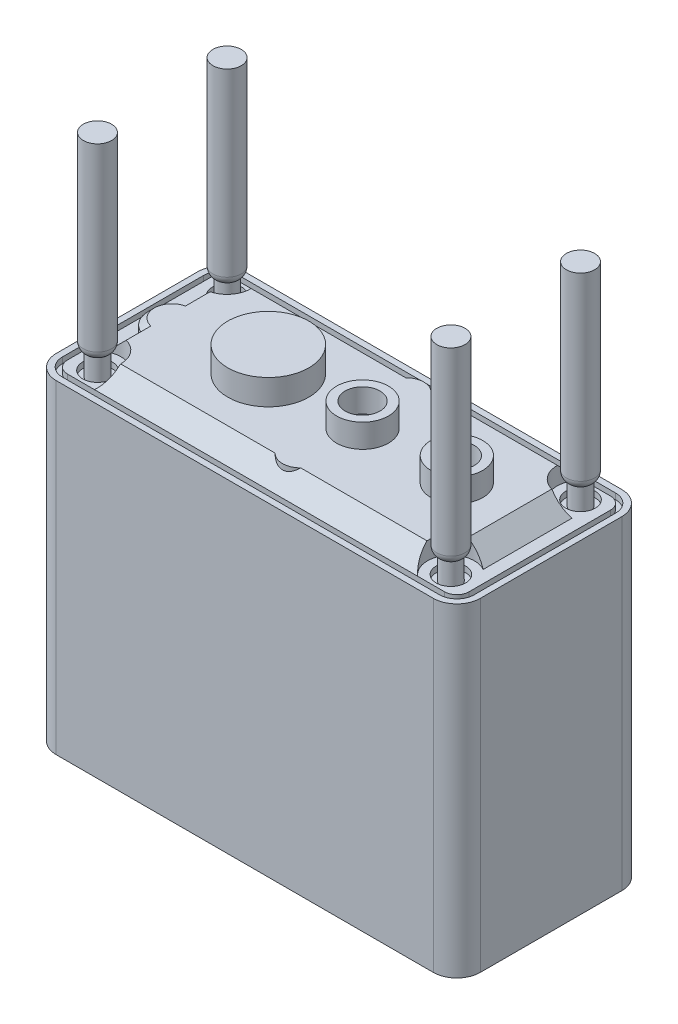
SolidWorks part; units mm, degrees
ref_plane "Front Plane" through (0, 0, 0) normal (0, 0, 1) x (1, 0, 0)
ref_plane "Top Plane" through (0, 0, 0) normal (0, 1, 0) x (1, 0, 0)
ref_plane "Right Plane" through (0, 0, 0) normal (1, 0, 0) x (0, 0, -1)
sketch "Sketch1" plane through (0, 0, 0) normal (0, 1, 0) x (1, 0, 0)
  line L1 (-28.575, 12.7) -> (28.575, 12.7)
  line L2 (-28.575, 12.7) -> (-28.575, -12.7)
  line L3 (-28.575, -12.7) -> (28.575, -12.7)
  line L4 (28.575, 12.7) -> (28.575, -12.7)
  line L5 (-28.575, 12.7) -> (28.575, -12.7) construction
  line L6 (-28.575, -12.7) -> (28.575, 12.7) construction
  point P0 (0, 0)
  dimension "D1" = 57.15
  dimension "D2" = 25.4
extrude "Boss-Extrude1" add sketch "Sketch1" along normal blind 43.6562
fillet "Fillet1" radius 3.175 4 edges at (-28.575, 21.8281, -12.7) (-28.575, 21.8281, 12.7) (28.575, 21.8281, -12.7) (28.575, 21.8281, 12.7)
sketch "Sketch2" plane through (0, 43.6562, 0) normal (0, 1, 0) x (1, 0, 0)
  line L8 (25.4, 11.8745) -> (-25.4, 11.8745)
  line L9 (-27.7495, 9.525) -> (-27.7495, -9.525)
  line L10 (-25.4, -11.8745) -> (25.4, -11.8745)
  line L11 (27.7495, -9.525) -> (27.7495, 9.525)
  line L12 (25.4, 11.8745) -> (-25.4, 11.8745)
  line L13 (-27.7495, 9.525) -> (-27.7495, -9.525)
  line L14 (-25.4, -11.8745) -> (25.4, -11.8745)
  line L15 (27.7495, -9.525) -> (27.7495, 9.525)
  line L20 (25.4, 11.176) -> (-25.4, 11.176)
  line L21 (-27.051, 9.525) -> (-27.051, -9.525)
  line L22 (-25.4, -11.176) -> (25.4, -11.176)
  line L23 (27.051, -9.525) -> (27.051, 9.525)
  line L24 (25.4, 11.176) -> (-25.4, 11.176)
  line L25 (-27.051, 9.525) -> (-27.051, -9.525)
  line L26 (-25.4, -11.176) -> (25.4, -11.176)
  line L27 (27.051, -9.525) -> (27.051, 9.525)
  arc A8 (-25.4, 11.8745) -> (-27.7495, 9.525) centre (-25.4, 9.525) ccw
  arc A9 (-27.7495, -9.525) -> (-25.4, -11.8745) centre (-25.4, -9.525) ccw
  arc A10 (25.4, -11.8745) -> (27.7495, -9.525) centre (25.4, -9.525) ccw
  arc A11 (27.7495, 9.525) -> (25.4, 11.8745) centre (25.4, 9.525) ccw
  arc A12 (-25.4, 11.8745) -> (-27.7495, 9.525) centre (-25.4, 9.525) ccw
  arc A13 (-27.7495, -9.525) -> (-25.4, -11.8745) centre (-25.4, -9.525) ccw
  arc A14 (25.4, -11.8745) -> (27.7495, -9.525) centre (25.4, -9.525) ccw
  arc A15 (27.7495, 9.525) -> (25.4, 11.8745) centre (25.4, 9.525) ccw
  arc A20 (-25.4, 11.176) -> (-27.051, 9.525) centre (-25.4, 9.525) ccw
  arc A21 (-27.051, -9.525) -> (-25.4, -11.176) centre (-25.4, -9.525) ccw
  arc A22 (25.4, -11.176) -> (27.051, -9.525) centre (25.4, -9.525) ccw
  arc A23 (27.051, 9.525) -> (25.4, 11.176) centre (25.4, 9.525) ccw
  arc A24 (-25.4, 11.176) -> (-27.051, 9.525) centre (-25.4, 9.525) ccw
  arc A25 (-27.051, -9.525) -> (-25.4, -11.176) centre (-25.4, -9.525) ccw
  arc A26 (25.4, -11.176) -> (27.051, -9.525) centre (25.4, -9.525) ccw
  arc A27 (27.051, 9.525) -> (25.4, 11.176) centre (25.4, 9.525) ccw
  dimension "D1" = 0.8255
  dimension "D2" = 1.524
extrude "Cut-Extrude1" cut sketch "Sketch2" against normal blind 0.7937
sketch "Sketch3" plane through (0, 43.6562, 0) normal (0, 1, 0) x (1, 0, 0)
  line L1 (23.8125, -8.7312) -> (-23.8125, -8.7313) construction
  line L2 (23.8125, -8.7312) -> (23.8125, 8.7313) construction
  line L3 (23.8125, 8.7313) -> (-23.8125, 8.7312) construction
  line L4 (-23.8125, -8.7313) -> (-23.8125, 8.7312) construction
  line L5 (23.8125, -8.7312) -> (-23.8125, 8.7312) construction
  line L6 (23.8125, 8.7313) -> (-23.8125, -8.7313) construction
  circle A0 centre (-23.8125, 8.7312) radius 1.9844
  circle A1 centre (-23.8125, -8.7313) radius 1.9844
  circle A2 centre (23.8125, -8.7312) radius 1.9844
  circle A3 centre (23.8125, 8.7313) radius 1.9844
  point P0 (0, 0)
  dimension "D1" = 3.9688
  dimension "D2" = 47.625
  dimension "D3" = 17.4625
extrude "Cut-Extrude2" cut sketch "Sketch3" against normal up to surface (0.7937 mm away) up to face at (0, 42.8625, 0)
sketch "Sketch4" plane through (0, 43.6562, 0) normal (0, 1, 0) x (1, 0, 0)
  line L1 (21.7867, -11.176) -> (-21.7867, -11.176)
  line L2 (25.4, -5.9816) -> (25.4, 5.9816)
  line L3 (21.7867, 11.176) -> (-21.7867, 11.176)
  line L4 (-25.4, -5.9816) -> (-25.4, 5.9816)
  line L5 (-25.4, -11.176) -> (25.4, -11.176) construction
  line L7 (25.4, 11.176) -> (-25.4, 11.176) construction
  arc A0 (-25.4, 5.9816) -> (-21.7867, 11.176) centre (-23.8125, 8.7312) ccw
  arc A1 (-21.7867, -11.176) -> (-25.4, -5.9816) centre (-23.8125, -8.7313) ccw
  arc A2 (25.4, -5.9816) -> (21.7867, -11.176) centre (23.8125, -8.7312) ccw
  arc A3 (21.7867, 11.176) -> (25.4, 5.9816) centre (23.8125, 8.7313) ccw
  point P0 (0, 0)
  point P1 (-21.7867, -11.176)
  point P4 (21.8281, -11.176)
  point P18 (21.8281, 11.176)
  point P27 (0, 0)
  point P28 (0, 0)
  point P29 (-25.0491, 11.176)
  dimension "D2" = 6.35
  dimension "D3" = 50.8
extrude "Boss-Extrude2" add sketch "Sketch4" along normal blind 2.3813
chamfer "Chamfer1" distance 2.3813 angle 45 4 edges at (25.4, 46.0375, 0) (0, 46.0375, -11.176) (-25.4, 46.0375, 0) (0, 46.0375, 11.176)
sketch "Sketch5" plane through (0, 46.0375, 0) normal (0, 1, 0) x (1, 0, 0)
  line L0 (-28.575, 9.525) -> (-28.575, -9.525) construction
  line L1 (1.905, -7.1437) -> (1.905, 0) construction
  line L2 (1.905, 0) -> (1.905, 7.1437) construction
  line L3 (-23.0187, 5.6571) -> (-23.0187, -5.6571) construction
  circle A0 centre (1.905, 7.1437) radius 2.3813
  circle A1 centre (1.905, -7.1437) radius 2.3813
  circle A2 centre (-22.5107, 0) radius 3.175
  point P12 (0, 0)
  dimension "D2" = 4.7625
  dimension "D4" = 6.35
  dimension "D1" = 30.48
  dimension "D3" = 7.1437
  dimension "D5" = 0.508
extrude "Boss-Extrude3" add sketch "Sketch5" against normal up to surface (2.3813 mm away) up to face at (-23.8125, 43.6562, -6.7469)
chamfer "Chamfer2" distance 0.7937 angle 45 1 edges at (-25.6857, 46.0375, 0)
sketch "Sketch6" plane through (0, 46.0375, 0) normal (0, 1, 0) x (1, 0, 0)
  line L0 (-9.525, 0) -> (3.175, 0) construction
  line L1 (3.175, 0) -> (15.875, 0) construction
  line L2 (28.575, -9.525) -> (28.575, 9.525) construction
  circle A0 centre (3.175, 0) radius 3.4925
  circle A1 centre (3.175, 0) radius 2.3495
  circle A2 centre (15.875, 0) radius 3.4925
  circle A3 centre (15.875, 0) radius 2.3495
  circle A4 centre (-9.525, 0) radius 5.461 construction
  point P10 (15.875, -0.4157)
  point P11 (0, 0)
  dimension "D1" = 10.922
  dimension "D3" = 6.985
  dimension "D4" = 4.699
  dimension "D2" = 12.7
  dimension "D5" = 12.7
extrude "Boss-Extrude4" add sketch "Sketch6" along normal blind 3.175
sketch "Sketch7" plane through (0, 46.0375, 0) normal (0, 1, 0) x (1, 0, 0)
  circle A0 centre (-9.525, 0) radius 5.461 construction
  circle A1 centre (-9.525, 0) radius 5.461
extrude "Boss-Extrude5" add sketch "Sketch7" along normal blind 3.429
sketch "Sketch8" plane through (0, 42.8625, 0) normal (0, 1, 0) x (1, 0, 0)
  circle A0 centre (-23.8125, -8.7313) radius 1.27
  circle A1 centre (23.8125, -8.7312) radius 1.27
  circle A2 centre (23.8125, 8.7313) radius 1.27
  circle A3 centre (-23.8125, 8.7312) radius 1.27
  dimension "D1" = 2.54
extrude "Boss-Extrude6" add sketch "Sketch8" along normal blind 3.175
sketch "Sketch9" plane through (0, 46.0375, 0) normal (0, 1, 0) x (1, 0, 0)
  circle A0 centre (-23.8125, -8.7313) radius 1.905
  circle A1 centre (-23.8125, 8.7312) radius 1.905
  circle A2 centre (23.8125, 8.7313) radius 1.905
  circle A3 centre (23.8125, -8.7312) radius 1.905
  dimension "D1" = 3.81
extrude "Boss-Extrude7" add sketch "Sketch9" along normal blind 25.4
fillet "Fillet2" radius 1.27 4 edges at (-23.8125, 46.0375, -6.8262) (23.8125, 46.0375, -6.8263) (23.8125, 46.0375, 10.6362) (-23.8125, 46.0375, 10.6363)
